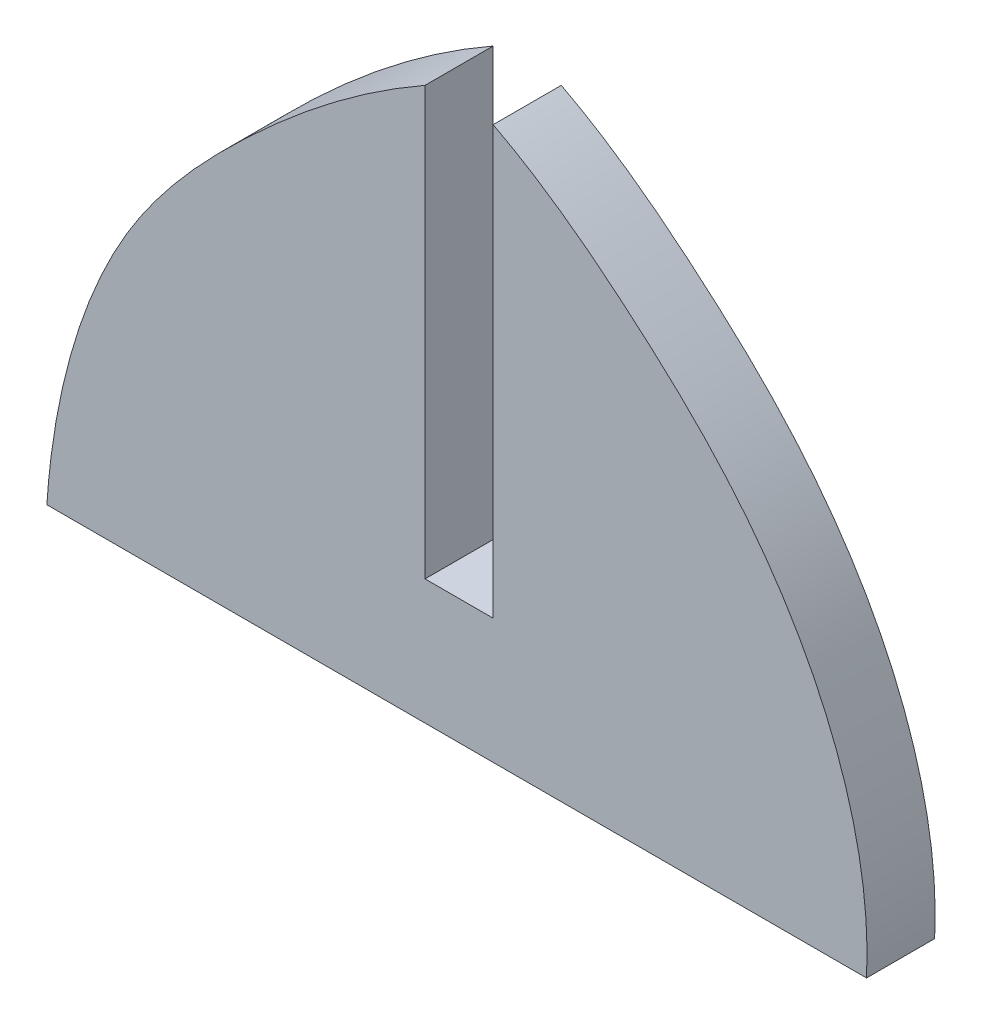
SolidWorks part; units mm, degrees
ref_plane "前视基准面" through (0, 0, 0) normal (0, 0, 1) x (1, 0, 0)
ref_plane "上视基准面" through (0, 0, 0) normal (0, 1, 0) x (1, 0, 0)
ref_plane "右视基准面" through (0, 0, 0) normal (1, 0, 0) x (0, 0, -1)
other "Configuration Table"
sketch "草图1" plane through (0, 0, 0) normal (0, 0, 1) x (1, 0, 0)
  line L0 (157.4101, 256.0211) -> (779.9201, 256.0211) construction
  line L1 (227.8199, 597.9035) -> (1733.8199, 597.9035) construction
  line L2 (376.5, 617) -> (1882.5, 617) construction
  line L3 (1224.6515, 227.8229) -> (1224.6515, 177.6192)
  line L4 (1224.6515, 177.6192) -> (1232.6515, 177.6192)
  line L5 (1232.6515, 177.6192) -> (1232.6515, 227.8229)
  line L6 (1180.2326, 162.9506) -> (1276.5081, 162.9506)
  line L7 (1228.6515, 177.6192) -> (1228.6515, 141.4603) construction
  line L8 (1228.6515, 177.6192) -> (1228.6515, 229.7658) construction
  spline S0 degree 3 poles (1232.6515, 227.8229) (1238.4415, 224.8136) (1248.9035, 216.9283) (1268.7088, 197.9725) (1277.228, 177.3544) (1276.5081, 162.9506) knots 0 0 0 0 0.237953 0.477618 1 1 1 1
  spline S1 degree 3 poles (1224.6515, 227.8229) (1216.7788, 223.3631) (1204.5326, 213.6554) (1185.8494, 193.222) (1180.9924, 174.5343) (1180.2326, 162.9506) knots 0 0 0 0 0.329523 0.570719 1 1 1 1
  dimension "D1" = 8
extrude "凸台-拉伸1" add sketch "草图1" along normal blind 8
